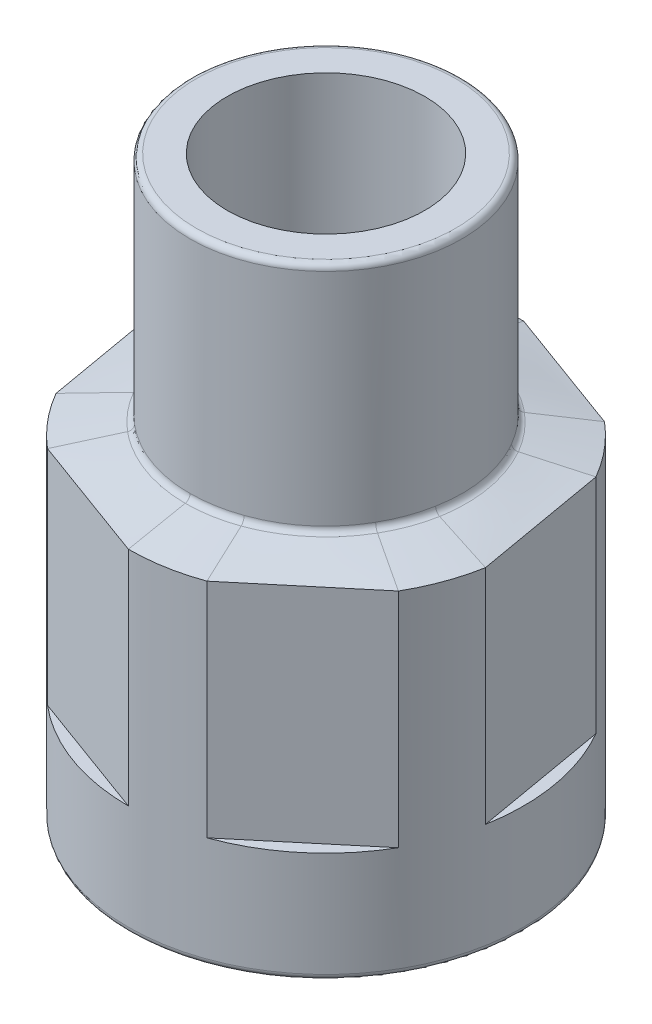
SolidWorks part; units mm, degrees
ref_plane "Спереди" through (0, 0, 0) normal (0, 0, 1) x (1, 0, 0)
ref_plane "Сверху" through (0, 0, 0) normal (0, 1, 0) x (1, 0, 0)
ref_plane "Справа" through (0, 0, 0) normal (1, 0, 0) x (0, 0, -1)
sketch "Эскиз1" plane through (0, 0, 0) normal (0, 1, 0) x (1, 0, 0)
  circle A0 centre (0, 0) radius 11
  dimension "D1" = 22
ref_plane "Плоскость1" through (0, -18.75, 0) normal (0, 1, 0) x (1, 0, 0)
sketch "Эскиз2" plane through (0, -18.75, 0) normal (0, 1, 0) x (1, 0, 0)
  circle A2 centre (0, 0) radius 11
  dimension "D1" = 22
loft "По сечениям1" add profiles "Эскиз2", "Эскиз1" connector at (-7.995, -18.75, -7.5552) connector at (-8.0065, 0, -7.5429)
cosmetic thread "Условное изображение резьбы3" parameters "D1"=15, "D2"=20.344
sketch "Эскиз3" plane through (0, 0, 0) normal (0, 1, 0) x (1, 0, 0)
  circle A0 centre (0, 0) radius 8
  circle A1 centre (0, 0) radius 11 construction
  dimension "D1" = 3
extrude "Вырез-Вытянуть1" cut sketch "Эскиз3" against normal blind 12
sketch "Эскиз4" plane through (0, -12, 0) normal (0, 1, 0) x (1, 0, 0)
  circle A0 centre (0, 0) radius 6.5
  circle A1 centre (0, 0) radius 8 construction
  dimension "D1" = 1.5
extrude "Вырез-Вытянуть2" cut sketch "Эскиз4" against normal through all
ref_plane "Плоскость2" through (0, -3.5, 0) normal (0, 1, 0) x (1, 0, 0)
ref_plane "Плоскость3" through (0, -19.75, 0) normal (0, 1, 0) x (1, 0, 0)
sketch "Эскиз6" plane through (0, -19.75, 0) normal (0, 1, 0) x (1, 0, 0)
  line L1 (-5.4169, 15.0551) -> (-13.8564, 8)
  line L2 (-15.7466, 2.8364) -> (-13.8564, -8)
  line L3 (-10.3297, -12.2187) -> (0, -16)
  line L4 (5.4169, -15.0551) -> (13.8564, -8)
  line L5 (15.7466, -2.8364) -> (13.8564, 8)
  line L6 (10.3297, 12.2188) -> (0, 16)
  arc A0 (-13.8564, 8) -> (-15.7466, 2.8364) centre (0, 0) ccw
  circle A1 centre (0, 0) radius 15.025 construction
  arc A2 (-13.8564, -8) -> (-10.3297, -12.2187) centre (0, 0) ccw
  arc A3 (0, 16) -> (-5.4169, 15.0551) centre (0, 0) ccw
  arc A4 (13.8564, 8) -> (10.3297, 12.2188) centre (0, 0) ccw
  arc A5 (13.8564, -8) -> (15.7466, -2.8364) centre (0, 0) ccw
  arc A6 (0, -16) -> (5.4169, -15.0551) centre (0, 0) ccw
  point P3 (-13.8564, 8)
  point P11 (-5.4169, 15.0551)
  dimension "D1" = 32
  dimension "D2" = 11
ref_plane "Плоскость4" through (0, -37.75, 0) normal (0, 1, 0) x (1, 0, 0)
sketch "Эскиз7" plane through (0, -37.75, 0) normal (0, 1, 0) x (1, 0, 0)
  line L0 (-10.3297, -12.2187) -> (0, -16) construction
  line L1 (5.4169, -15.0551) -> (13.8564, -8) construction
  line L2 (15.7466, -2.8364) -> (13.8564, 8) construction
  line L3 (10.3297, 12.2188) -> (0, 16) construction
  line L4 (-5.4169, 15.0551) -> (-13.8564, 8) construction
  line L5 (-15.7466, 2.8364) -> (-13.8564, -8) construction
  line L6 (-10.3297, -12.2187) -> (0, -16)
  line L7 (5.4169, -15.0551) -> (13.8564, -8)
  line L8 (15.7466, -2.8364) -> (13.8564, 8)
  line L9 (10.3297, 12.2188) -> (0, 16)
  line L10 (-5.4169, 15.0551) -> (-13.8564, 8)
  line L11 (-15.7466, 2.8364) -> (-13.8564, -8)
  arc A0 (0, -16) -> (5.4169, -15.0551) centre (0, 0) ccw construction
  arc A1 (13.8564, -8) -> (15.7466, -2.8364) centre (0, 0) ccw construction
  arc A2 (13.8564, 8) -> (10.3297, 12.2188) centre (0, 0) ccw construction
  arc A3 (0, 16) -> (-5.4169, 15.0551) centre (0, 0) ccw construction
  arc A4 (-13.8564, 8) -> (-15.7466, 2.8364) centre (0, 0) ccw construction
  arc A5 (-13.8564, -8) -> (-10.3297, -12.2187) centre (0, 0) ccw construction
  arc A6 (0, -16) -> (5.4169, -15.0551) centre (0, 0) ccw
  arc A7 (13.8564, -8) -> (15.7466, -2.8364) centre (0, 0) ccw
  arc A8 (13.8564, 8) -> (10.3297, 12.2188) centre (0, 0) ccw
  arc A9 (0, 16) -> (-5.4169, 15.0551) centre (0, 0) ccw
  arc A10 (-13.8564, 8) -> (-15.7466, 2.8364) centre (0, 0) ccw
  arc A11 (-13.8564, -8) -> (-10.3297, -12.2187) centre (0, 0) ccw
loft "По сечениям2" add profiles "Эскиз6", "Эскиз2<3>" connector at (15.7466, -19.75, 2.8364) connector at (-8.4845, -18.75, -7.001)
sketch "Эскиз2<3>" plane through (0, -18.75, 0) normal (0, 1, 0) x (1, 0, 0) same geometry as "Эскиз2"
loft "По сечениям3" add profiles "Эскиз7", "Эскиз6<3>" connector at (-13.8564, -37.75, 8) connector at (-13.8564, -19.75, 8)
sketch "Эскиз6<3>" plane through (0, -19.75, 0) normal (0, 1, 0) x (1, 0, 0) same geometry as "Эскиз6"
sketch "Эскиз8" plane through (0, -37.75, 0) normal (0, 1, 0) x (1, 0, 0)
  circle A0 centre (0, 0) radius 16
  dimension "D1" = 32
ref_plane "Плоскость5" through (0, -46.75, 0) normal (0, 1, 0) x (1, 0, 0)
sketch "Эскиз9" plane through (0, -46.75, 0) normal (0, 1, 0) x (1, 0, 0)
  circle A0 centre (0, 0) radius 16 construction
  circle A1 centre (0, 0) radius 16
extrude "Бобышка-Вытянуть1" add sketch "Эскиз8" against normal blind 9 contours A0
ref_plane "Плоскость6" through (0, -47.75, 0) normal (0, 1, 0) x (1, 0, 0)
sketch "Эскиз10" plane through (0, -47.75, 0) normal (0, 1, 0) x (1, 0, 0)
  circle A0 centre (0, 0) radius 13.9
  dimension "D1" = 27.8
extrude "Бобышка-Вытянуть2" add sketch "Эскиз10" along normal blind 1
sketch "Эскиз11" plane through (0, -47.75, 0) normal (0, -1, 0) x (1, 0, 0)
  circle A0 centre (0, 0) radius 10
  dimension "D1" = 20
extrude "Вырез-Вытянуть3" cut sketch "Эскиз11" against normal blind 20
cosmetic thread "Условное изображение резьбы4" parameters "D2"=22
sketch "Эскиз12" plane through (0, -27.75, 0) normal (0, -1, 0) x (1, 0, 0)
  circle A0 centre (0, 0) radius 7
  circle A1 centre (0, 0) radius 10 construction
  dimension "D1" = 3
ref_plane "Плоскость7" through (0, -18.75, 0) normal (0, 1, 0) x (1, 0, 0)
extrude "Вырез-Вытянуть4" cut sketch "Эскиз12" against normal up to surface (9 mm away) up to plane "Плоскость7"
fillet "Скругление1" radius 0.5 12 edges
sketch "Эскиз13" plane through (0, -3.5, 0) normal (0, 1, 0) x (1, 0, 0)
  circle A0 centre (0, 0) radius 11 construction
  circle A1 centre (0, 0) radius 11
fillet "Скругление2" radius 0.5 1 edges at (0, -46.75, 16)
fillet "Скругление3" radius 0.2 1 edges at (0, -46.75, 13.9)
fillet "Скругление4" radius 0.2 1 edges at (0, -47.75, 13.9)
fillet "Скругление5" radius 0.5 1 edges at (0, 0, 11)
